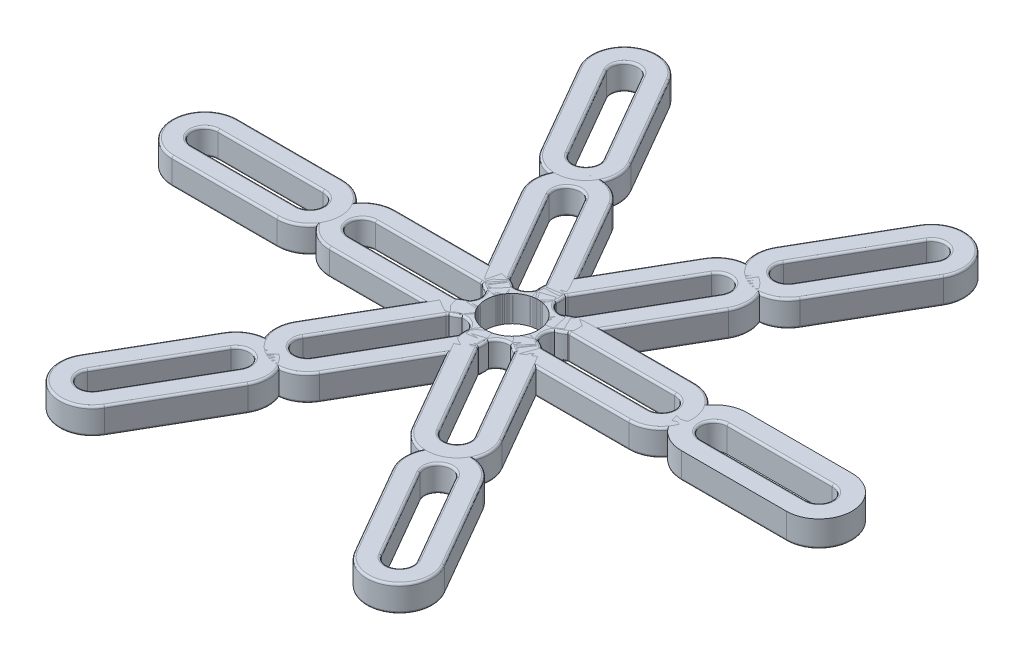
SolidWorks part; units mm, degrees
material "PET"
ref_plane "Front Plane" through (0, 0, 0) normal (0, 0, 1) x (1, 0, 0)
ref_plane "Top Plane" through (0, 0, 0) normal (0, 1, 0) x (1, 0, 0)
ref_plane "Right Plane" through (0, 0, 0) normal (1, 0, 0) x (0, 0, -1)
ref_axis "X-Axis" through (-88.99, 0, 0) along (1, 0, 0)
ref_axis "Y-Axis" through (0, 55, 0) along (0, -1, 0)
ref_axis "Z-Axis" through (0, 0, -88.99) along (0, 0, 1)
sketch "Sketch1" plane through (0, 0, 0) normal (0, 1, 0) x (1, 0, 0)
  circle A0 centre (0, 0) radius 41.275 construction
  dimension "D1" = 82.55
sketch "Sketch2" plane through (0, 0, 0) normal (0, 1, 0) x (1, 0, 0)
  line L0 (5.3975, 0) -> (18.0975, 0) construction
  line L1 (5.3975, 1.5875) -> (18.0975, 1.5875)
  line L2 (5.3975, -1.5875) -> (18.0975, -1.5875)
  line L3 (19.685, 7.0845) -> (19.685, -8.4398) construction
  line L4 (21.2725, 7.0845) -> (21.2725, -8.4398) construction
  line L6 (37.1475, 0) -> (24.4475, 0) construction
  line L7 (37.1475, 1.5875) -> (24.4475, 1.5875)
  line L8 (37.1475, -1.5875) -> (24.4475, -1.5875)
  line L9 (2.6987, -4.6744) -> (9.0487, -15.6729) construction
  line L10 (4.0736, -3.8806) -> (10.4236, -14.8791)
  line L11 (1.3239, -5.4681) -> (7.6739, -16.4666)
  line L12 (18.5737, -32.1707) -> (12.2237, -21.1722) construction
  line L13 (19.9486, -31.3769) -> (13.5986, -20.3784)
  line L14 (17.1989, -32.9644) -> (10.8489, -21.9659)
  line L15 (-2.6988, -4.6744) -> (-9.0488, -15.6729) construction
  line L16 (-1.3239, -5.4681) -> (-7.6739, -16.4666)
  line L17 (-4.0736, -3.8806) -> (-10.4236, -14.8791)
  line L18 (-18.5738, -32.1707) -> (-12.2238, -21.1722) construction
  line L19 (-17.1989, -32.9644) -> (-10.8489, -21.9659)
  line L20 (-19.9486, -31.3769) -> (-13.5986, -20.3784)
  line L21 (-5.3975, 0) -> (-18.0975, 0) construction
  line L22 (-5.3975, -1.5875) -> (-18.0975, -1.5875)
  line L23 (-5.3975, 1.5875) -> (-18.0975, 1.5875)
  line L24 (-37.1475, 0) -> (-24.4475, 0) construction
  line L25 (-37.1475, -1.5875) -> (-24.4475, -1.5875)
  line L26 (-37.1475, 1.5875) -> (-24.4475, 1.5875)
  line L27 (-2.6987, 4.6744) -> (-9.0487, 15.6729) construction
  line L28 (-4.0736, 3.8806) -> (-10.4236, 14.8791)
  line L29 (-1.3239, 5.4681) -> (-7.6739, 16.4666)
  line L30 (-18.5737, 32.1707) -> (-12.2237, 21.1722) construction
  line L31 (-19.9486, 31.3769) -> (-13.5986, 20.3784)
  line L32 (-17.1989, 32.9644) -> (-10.8489, 21.9659)
  line L33 (2.6988, 4.6744) -> (9.0488, 15.6729) construction
  line L34 (1.3239, 5.4681) -> (7.6739, 16.4666)
  line L35 (4.0736, 3.8806) -> (10.4236, 14.8791)
  line L36 (18.5738, 32.1707) -> (12.2238, 21.1722) construction
  line L37 (17.1989, 32.9644) -> (10.8489, 21.9659)
  line L38 (19.9486, 31.3769) -> (13.5986, 20.3784)
  circle A0 centre (0, 0) radius 3.81 construction
  arc A1 (5.3975, 1.5875) -> (5.3975, -1.5875) centre (5.3975, 0) ccw
  arc A2 (18.0975, -1.5875) -> (18.0975, 1.5875) centre (18.0975, 0) ccw
  arc A3 (37.1475, 1.5875) -> (37.1475, -1.5875) centre (37.1475, 0) cw
  arc A4 (24.4475, -1.5875) -> (24.4475, 1.5875) centre (24.4475, 0) cw
  arc A5 (4.0736, -3.8806) -> (1.3239, -5.4681) centre (2.6987, -4.6744) ccw
  arc A6 (7.6739, -16.4666) -> (10.4236, -14.8791) centre (9.0487, -15.6729) ccw
  arc A7 (19.9486, -31.3769) -> (17.1989, -32.9644) centre (18.5737, -32.1707) cw
  arc A8 (10.8489, -21.9659) -> (13.5986, -20.3784) centre (12.2237, -21.1722) cw
  arc A9 (-1.3239, -5.4681) -> (-4.0736, -3.8806) centre (-2.6988, -4.6744) ccw
  arc A10 (-10.4236, -14.8791) -> (-7.6739, -16.4666) centre (-9.0488, -15.6729) ccw
  arc A11 (-17.1989, -32.9644) -> (-19.9486, -31.3769) centre (-18.5738, -32.1707) cw
  arc A12 (-13.5986, -20.3784) -> (-10.8489, -21.9659) centre (-12.2238, -21.1722) cw
  arc A13 (-5.3975, -1.5875) -> (-5.3975, 1.5875) centre (-5.3975, 0) ccw
  arc A14 (-18.0975, 1.5875) -> (-18.0975, -1.5875) centre (-18.0975, 0) ccw
  arc A15 (-37.1475, -1.5875) -> (-37.1475, 1.5875) centre (-37.1475, 0) cw
  arc A16 (-24.4475, 1.5875) -> (-24.4475, -1.5875) centre (-24.4475, 0) cw
  arc A17 (-4.0736, 3.8806) -> (-1.3239, 5.4681) centre (-2.6987, 4.6744) ccw
  arc A18 (-7.6739, 16.4666) -> (-10.4236, 14.8791) centre (-9.0487, 15.6729) ccw
  arc A19 (-19.9486, 31.3769) -> (-17.1989, 32.9644) centre (-18.5737, 32.1707) cw
  arc A20 (-10.8489, 21.9659) -> (-13.5986, 20.3784) centre (-12.2237, 21.1722) cw
  arc A21 (1.3239, 5.4681) -> (4.0736, 3.8806) centre (2.6988, 4.6744) ccw
  arc A22 (10.4236, 14.8791) -> (7.6739, 16.4666) centre (9.0488, 15.6729) ccw
  arc A23 (17.1989, 32.9644) -> (19.9486, 31.3769) centre (18.5738, 32.1707) cw
  arc A24 (13.5986, 20.3784) -> (10.8489, 21.9659) centre (12.2238, 21.1722) cw
  point P5 (11.7475, 0)
  point P11 (3.81, 0)
  point P17 (30.7975, 0)
  point P27 (5.8737, -10.1736)
  point P34 (15.3987, -26.6714)
  point P41 (-5.8738, -10.1736)
  point P48 (-15.3988, -26.6714)
  point P55 (-11.7475, 0)
  point P62 (-30.7975, 0)
  point P69 (-5.8737, 10.1736)
  point P76 (-15.3987, 26.6714)
  point P83 (5.8738, 10.1736)
  point P90 (15.3988, 26.6714)
  dimension "D1" = 7.62
  dimension "D3" = 3.175
  dimension "D4" = 1.5875
  dimension "D2" = 12.7
  dimension "D5" = 6
extrude "Extrude-Thin1" add sketch "Sketch2" along normal blind 3.175 thin thin type one direction wall 2.3876
sketch "Sketch3" plane through (0, 0, 0) normal (0, 1, 0) x (1, 0, 0)
  circle A0 centre (0, 0) radius 3.175
  dimension "D1" = 6.35
extrude "Cut-Extrude1" cut sketch "Sketch3" along normal blind 3.175
fillet "Fillet3" radius 0.254 18 edges at (3.81, 0, 0) (11.7475, 0, -1.5875) (19.685, 0, 0) (3.5831, 0, 3.5369) (3.5831, 0, -3.5369) (11.7475, 0, -3.9751) (22.0726, 0, 0) (3.5831, 3.175, 3.5369) (11.7475, 3.175, 3.9751) (22.0726, 3.175, 0) (3.5831, 3.175, -3.5369) (3.81, 3.175, 0) (11.7475, 3.175, -1.5875) (19.685, 3.175, 0) (11.7475, 0, 1.5875) (11.7475, 0, 3.9751) (11.7475, 3.175, -3.9751) (11.7475, 3.175, 1.5875)
fillet "Fillet4" radius 0.254 8 edges at (30.7975, 0, -3.9751) (20.4724, 0, 0) (30.7975, 0, 3.9751) (41.1226, 0, 0) (30.7975, 3.175, -1.5875) (22.86, 3.175, 0) (30.7975, 3.175, 1.5875) (38.735, 3.175, 0)
fillet "Fillet5" radius 0.254 18 edges at (4.8546, 0, -1.3346) (-1.2715, 0, -4.8715) (2.4312, 0, -12.1612) (11.0363, 0, -19.1154) (1.905, 0, -3.2996) (4.4989, 0, -10.9674) (9.8425, 0, -17.0477) (4.8546, 3.175, -1.3346) (-1.2715, 3.175, -4.8715) (2.4312, 3.175, -12.1612) (11.0363, 3.175, -19.1154) (9.8425, 3.175, -17.0477) (7.2486, 3.175, -9.3799) (1.905, 3.175, -3.2996) (9.3163, 0, -8.1861) (7.2486, 0, -9.3799) (9.3163, 3.175, -8.1861) (4.4989, 3.175, -10.9674)
fillet "Fillet6" radius 0.254 16 edges at (19.3675, 3.175, -33.5455) (16.7736, 3.175, -25.8777) (11.43, 3.175, -19.7973) (20.5613, 3.175, -35.6132) (18.8413, 3.175, -24.6839) (10.2362, 3.175, -17.7296) (10.2362, 0, -17.7296) (11.9562, 0, -28.659) (20.5613, 0, -35.6132) (11.43, 0, -19.7973) (14.0239, 0, -27.4652) (19.3675, 0, -33.5455) (14.0239, 3.175, -27.4652) (11.9562, 3.175, -28.659) (18.8413, 0, -24.6839) (16.7736, 0, -25.8777)
fillet "Fillet7" radius 0.254 18 edges at (-1.905, 0, -3.2996) (-7.2486, 0, -9.3799) (-9.8425, 0, -17.0477) (1.2715, 0, -4.8715) (-4.8546, 0, -1.3346) (-9.3163, 0, -8.1861) (-11.0363, 0, -19.1154) (1.2715, 3.175, -4.8715) (-4.8546, 3.175, -1.3346) (-9.3163, 3.175, -8.1861) (-11.0363, 3.175, -19.1154) (-1.905, 3.175, -3.2996) (-7.2486, 3.175, -9.3799) (-9.8425, 3.175, -17.0477) (-4.4989, 0, -10.9674) (-2.4312, 0, -12.1612) (-2.4312, 3.175, -12.1612) (-4.4989, 3.175, -10.9674)
fillet "Fillet8" radius 0.254 16 edges at (-11.43, 3.175, -19.7973) (-16.7736, 3.175, -25.8777) (-19.3675, 3.175, -33.5455) (-10.2362, 3.175, -17.7296) (-18.8413, 3.175, -24.6839) (-20.5613, 3.175, -35.6132) (-10.2362, 0, -17.7296) (-18.8413, 0, -24.6839) (-20.5613, 0, -35.6132) (-11.43, 0, -19.7973) (-16.7736, 0, -25.8777) (-19.3675, 0, -33.5455) (-14.0239, 3.175, -27.4652) (-11.9562, 3.175, -28.659) (-11.9562, 0, -28.659) (-14.0239, 0, -27.4652)
fillet "Fillet9" radius 0.254 18 edges at (-3.5831, 0, -3.5369) (-11.7475, 0, -3.9751) (-22.0726, 0, 0) (-3.5831, 0, 3.5369) (-3.81, 0, 0) (-11.7475, 0, 1.5875) (-19.685, 0, 0) (-3.5831, 3.175, -3.5369) (-11.7475, 3.175, -3.9751) (-22.0726, 3.175, 0) (-3.5831, 3.175, 3.5369) (-19.685, 3.175, 0) (-11.7475, 3.175, -1.5875) (-3.81, 3.175, 0) (-11.7475, 0, 3.9751) (-11.7475, 0, -1.5875) (-11.7475, 3.175, 3.9751) (-11.7475, 3.175, 1.5875)
fillet "Fillet10" radius 0.254 16 edges at (-38.735, 3.175, 0) (-30.7975, 3.175, -1.5875) (-22.86, 3.175, 0) (-41.1226, 3.175, 0) (-30.7975, 3.175, -3.9751) (-20.4724, 3.175, 0) (-41.1226, 0, 0) (-30.7975, 0, -3.9751) (-20.4724, 0, 0) (-38.735, 0, 0) (-30.7975, 0, -1.5875) (-22.86, 0, 0) (-30.7975, 3.175, 1.5875) (-30.7975, 3.175, 3.9751) (-30.7975, 0, 3.9751) (-30.7975, 0, 1.5875)
fillet "Fillet11" radius 0.254 18 edges at (-9.8425, 0, 17.0477) (-7.2486, 0, 9.3799) (-1.905, 0, 3.2996) (-4.8546, 0, 1.3346) (-9.3163, 0, 8.1861) (-11.0363, 0, 19.1154) (1.2715, 0, 4.8715) (-4.8546, 3.175, 1.3346) (-9.3163, 3.175, 8.1861) (-11.0363, 3.175, 19.1154) (1.2715, 3.175, 4.8715) (-1.905, 3.175, 3.2996) (-4.4989, 3.175, 10.9674) (-9.8425, 3.175, 17.0477) (-4.4989, 0, 10.9674) (-2.4312, 0, 12.1612) (-2.4312, 3.175, 12.1612) (-7.2486, 3.175, 9.3799)
fillet "Fillet12" radius 0.254 16 edges at (-19.3675, 3.175, 33.5455) (-16.7736, 3.175, 25.8777) (-11.43, 3.175, 19.7973) (-20.5613, 3.175, 35.6132) (-18.8413, 3.175, 24.6839) (-10.2362, 3.175, 17.7296) (-20.5613, 0, 35.6132) (-18.8413, 0, 24.6839) (-10.2362, 0, 17.7296) (-11.43, 0, 19.7973) (-14.0239, 0, 27.4652) (-19.3675, 0, 33.5455) (-14.0239, 3.175, 27.4652) (-11.9562, 3.175, 28.659) (-11.9562, 0, 28.659) (-16.7736, 0, 25.8777)
fillet "Fillet13" radius 0.254 18 edges at (1.905, 0, 3.2996) (7.2486, 0, 9.3799) (9.8425, 0, 17.0477) (-1.2715, 0, 4.8715) (4.8546, 0, 1.3346) (9.3163, 0, 8.1861) (11.0363, 0, 19.1154) (-1.2715, 3.175, 4.8715) (4.8546, 3.175, 1.3346) (9.3163, 3.175, 8.1861) (11.0363, 3.175, 19.1154) (1.905, 3.175, 3.2996) (7.2486, 3.175, 9.3799) (9.8425, 3.175, 17.0477) (4.4989, 0, 10.9674) (2.4312, 0, 12.1612) (2.4312, 3.175, 12.1612) (4.4989, 3.175, 10.9674)
fillet "Fillet14" radius 0.254 16 edges at (20.5613, 3.175, 35.6132) (11.9562, 3.175, 28.659) (10.2362, 3.175, 17.7296) (19.3675, 3.175, 33.5455) (14.0239, 3.175, 27.4652) (11.43, 3.175, 19.7973) (10.2362, 0, 17.7296) (18.8413, 0, 24.6839) (20.5613, 0, 35.6132) (11.43, 0, 19.7973) (16.7736, 0, 25.8777) (19.3675, 0, 33.5455) (18.8413, 3.175, 24.6839) (16.7736, 3.175, 25.8777) (11.9562, 0, 28.659) (14.0239, 0, 27.4652)
